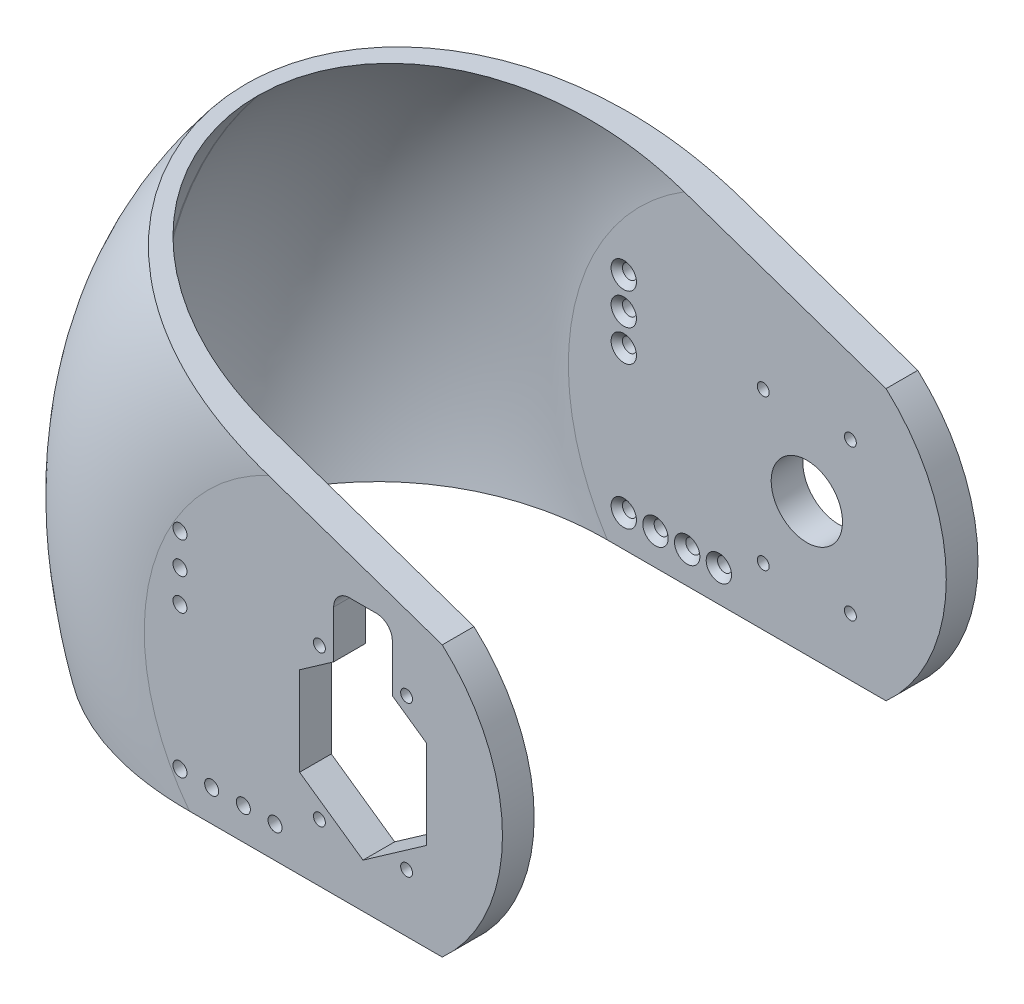
SolidWorks part; units mm, degrees
ref_plane "Front Plane" through (0, 0, 0) normal (0, 0, 1) x (1, 0, 0)
ref_plane "Top Plane" through (0, 0, 0) normal (0, 1, 0) x (1, 0, 0)
ref_plane "Right Plane" through (0, 0, 0) normal (1, 0, 0) x (0, 0, -1)
sketch "Sketch1" plane through (0, 0, 0) normal (0, 0, 1) x (1, 0, 0)
  line L0 (31.75, -53.34) -> (-174.9284, -53.34)
  line L2 (-142.2685, 114.912) -> (31.75, 54.9926)
  line L3 (31.75, 54.9926) -> (0, 0) construction
  line L4 (0, 0) -> (86.4977, 0) construction
  line L6 (-17.4625, 30.1625) -> (17.4625, 30.1625) construction
  line L7 (-17.4625, 30.1625) -> (-17.4625, -30.1625) construction
  line L8 (-17.4625, -30.1625) -> (17.4625, -30.1625) construction
  line L9 (17.4625, 30.1625) -> (17.4625, -30.1625) construction
  circle A0 centre (0, 0) radius 50.8 construction
  circle A1 centre (0, 0) radius 14.2875
  arc A4 (-142.2685, 114.912) -> (-174.9284, -53.34) centre (0, 0) ccw
  arc A10 (31.75, 54.9926) -> (31.75, -53.34) centre (-16.9805, 0.8263) cw
  circle A11 centre (-17.4625, 30.1625) radius 2.3813
  circle A12 centre (17.4625, 30.1625) radius 2.3813
  circle A13 centre (17.4625, -30.1625) radius 2.3813
  circle A14 centre (-17.4625, -30.1625) radius 2.3813
  circle A15 centre (-98.7284, -40.64) radius 2.3813 construction
  circle A16 centre (-86.0284, -40.64) radius 2.3813 construction
  circle A17 centre (-73.3284, -40.64) radius 2.3813 construction
  circle A18 centre (-60.6284, -40.64) radius 2.3812 construction
  circle A23 centre (-86.0284, 41.91) radius 2.3813 construction
  circle A24 centre (-86.0284, 29.21) radius 2.3813 construction
  circle A25 centre (-86.0284, 16.51) radius 2.3813 construction
  point P19 (0, 30.1625)
  point P21 (-17.4625, 0)
  point P32 (-179.529, 34.8489)
  point P38 (55.88, 0.8263)
  dimension "D1" = 101.6
  dimension "D2" = 28.575
  dimension "D9" = 63.5
  dimension "D10" = 76.2
  dimension "D11" = 4
  dimension "D13" = 182.88
  dimension "D3" = 19
  dimension "D6" = 53.34
  dimension "D4" = 4.7625
  dimension "D5" = 12.7
  dimension "D7" = 55.88
  dimension "D16" = 4.7625
  dimension "D17" = 4.7625
  dimension "D8" = 60
  dimension "D12" = 12.7
  dimension "D14" = 60.325
  dimension "D15" = 34.925
  dimension "D18" = 12.7
  dimension "D19" = 12.7
  dimension "D20" = 57.15
extrude "Boss-Extrude1" add sketch "Sketch1" against normal blind 190.5
sketch "Sketch2" plane through (0, -53.34, 0) normal (0, -1, 0) x (1, 0, 0)
  line L0 (-182.88, 0) -> (-182.88, -190.5) construction
  line L1 (-182.88, -12.7) -> (55.88, -12.7)
  line L2 (-182.88, -12.7) -> (-182.88, -177.8)
  line L3 (-182.88, -177.8) -> (55.88, -177.8)
  line L6 (-174.9284, 0) -> (31.75, 0) construction
  line L7 (55.88, -190.5) -> (55.88, 0) construction
  line L8 (55.88, -12.7) -> (55.88, -177.8)
  line L9 (-182.88, 0) -> (-182.88, -190.5) construction
  dimension "D1" = 165.1
  dimension "D2" = 12.7
extrude "Cut-Extrude1" cut sketch "Sketch2" against normal through all
sketch "Sketch3" plane through (0, 0, -177.8) normal (0, 0, 1) x (1, 0, 0)
  line L0 (-142.2685, 114.912) -> (-137.4653, 113.2581)
  line L2 (-174.9284, -53.34) -> (-169.8484, -53.34)
  line L3 (-174.9284, -53.34) -> (31.75, -53.34) construction
  arc A0 (-174.9284, -53.34) -> (-142.2685, 114.912) centre (0, 0) cw
  arc A1 (-142.2685, 114.912) -> (-174.9284, -53.34) centre (0, 0) ccw construction
  arc A2 (-169.8484, -53.34) -> (-137.4653, 113.2581) centre (2.2196, -0.34) cw
  point P14 (-179.529, 34.8489)
  point P15 (-174.518, 34.014)
  dimension "D1" = 5.08
  dimension "D2" = 5.08
  dimension "D3" = 5.08
  dimension "D4" = 19
extrude "Boss-Extrude2" add sketch "Sketch3" along normal up to next (165.1 mm away)
sketch "Sketch5" plane through (0, 0, 0) normal (0, 0, 1) x (1, 0, 0)
  line L0 (-25.4, 17.78) -> (-25.4, -17.78)
  line L1 (25.4, -17.78) -> (25.4, 17.78)
  line L2 (-25.4, -17.78) -> (0, -35.5653)
  line L4 (0, -35.5653) -> (25.4, -17.78)
  line L5 (25.4, 17.78) -> (11.7475, 27.3396)
  line L7 (-11.7475, 27.3396) -> (-25.4, 17.78)
  line L8 (-11.7475, 27.3396) -> (-11.7475, 46.3896)
  line L9 (-5.3975, 52.7396) -> (5.3975, 52.7396)
  line L10 (11.7475, 46.3896) -> (11.7475, 27.3396)
  arc A0 (-11.7475, 46.3896) -> (-5.3975, 52.7396) centre (-5.3975, 46.3896) cw
  arc A1 (5.3975, 52.7396) -> (11.7475, 46.3896) centre (5.3975, 46.3896) cw
  point P9 (-25.4, 0)
  point P16 (-11.7475, 52.7396)
  point P19 (11.7475, 52.7396)
  dimension "D8" = 6.35
  dimension "D1" = 125
  dimension "D2" = 35.56
  dimension "D3" = 50.8
  dimension "D4" = 125
  dimension "D5" = 23.495
  dimension "D6" = 125
  dimension "D7" = 25.4
extrude "Cut-Extrude3" cut sketch "Sketch5" against normal up to body
fillet "Fillet2" radius 82.296 2 edges at (-174.518, 34.014, -12.7) (-174.518, 34.014, -177.8)
fillet "Fillet3" radius 95.25 2 edges at (-179.529, 34.8489, -190.5) (-179.529, 34.8489, 0)
sketch "Sketch6" plane through (0, 0, 0) normal (0, 0, 1) x (1, 0, 0)
  line L0 (-69.526, -53.34) -> (31.75, -53.34) construction
  circle A0 centre (-73.3284, 41.91) radius 2.3813 construction
  circle A1 centre (-73.3284, 29.21) radius 2.3813 construction
  circle A2 centre (-73.3284, 16.51) radius 2.3813 construction
  circle A5 centre (-73.3284, -40.64) radius 2.3813 construction
  circle A6 centre (-60.6284, -40.64) radius 2.3812 construction
  circle A7 centre (-47.9284, -40.64) radius 2.3812 construction
  circle A8 centre (-35.2284, -40.64) radius 2.3812 construction
  point P0 (-73.3284, 41.91)
  point P2 (-73.3284, 29.21)
  point P4 (-73.3284, 16.51)
  point P12 (-73.3284, -40.64)
  point P14 (-60.6284, -40.64)
  dimension "D3" = 4.7625
  dimension "D5" = 92.3784
  dimension "D6" = 4.7625
  dimension "D1" = 12.7
  dimension "D2" = 12.7
  dimension "D4" = 69.85
  dimension "D7" = 12.7
  dimension "D8" = 12.7
  dimension "D9" = 12.7
  dimension "D10" = 12.7
sketch "Sketch15" plane through (0, 0, -12.7) normal (0, 0, -1) x (-1, 0, 0)
  line L2 (-31.75, -53.34) -> (79.9142, -53.34)
  line L3 (49.1236, 82.8396) -> (-31.75, 54.9926)
  line L4 (-31.75, -53.34) -> (79.9142, -53.34)
  line L5 (49.1236, 82.8396) -> (-31.75, 54.9926)
  circle A0 centre (73.3284, 29.21) radius 2.3813 construction
  circle A1 centre (73.3284, 29.21) radius 2.3813 construction
  arc A2 (79.9142, -53.34) -> (49.1236, 82.8396) centre (-2.2196, -0.34) ccw
  arc A3 (-31.75, 54.9926) -> (-31.75, -53.34) centre (16.9805, 0.8263) ccw
  arc A4 (79.9142, -53.34) -> (49.1236, 82.8396) centre (-2.2196, -0.34) ccw
  arc A5 (-31.75, 54.9926) -> (-31.75, -53.34) centre (16.9805, 0.8263) ccw
  point P2 (73.3284, 29.21)
  point P23 (73.3284, 41.91)
  point P26 (73.3284, 16.51)
  point P37 (60.6284, -40.64)
  point P74 (73.3284, -40.64)
  point P180 (47.9284, -40.64)
  point P183 (35.2284, -40.64)
  dimension "D1" = 0
hole_wizard "CSK for #10 Flat Head Machine Screw (100)12" positions "Sketch15" profile "Sketch17" countersink size "#10" standard "ANSI Inch" end condition through all
sketch "Sketch17" plane through (-35.2284, -40.64, -12.7) normal (1, 0, 0) x (0, 1, 0)
  line L0 (0, 0) -> (0, 21.3048)
  line L1 (0, 21.3048) -> (2.8067, 21.3048)
  line L2 (2.8067, 21.3048) -> (2.8067, 2.2733)
  line L3 (2.8067, 2.2733) -> (5.08, 0)
  line L5 (5.08, 0) -> (0, 0)
  line L6 (-2.8067, 2.2733) -> (-5.08, 0) construction
  line L11 (0, -6.35) -> (0, 107.95) construction
  dimension "Thru Hole Dia." = 5.6134
  dimension "Thru Hole Depth" = 21.3048
  dimension "Near C'Sink Dia." = 10.16
  dimension "Near C'Sink Angle" = 90
ref_plane "Plane1" through (0, 0, -95.25) normal (0, 0, -1) x (-1, 0, 0)
mirror "Mirror1" about plane through (0, 0, -95.25) normal (0, 0, -1) of "CSK for #10 Flat Head Machine Screw (100)12"
